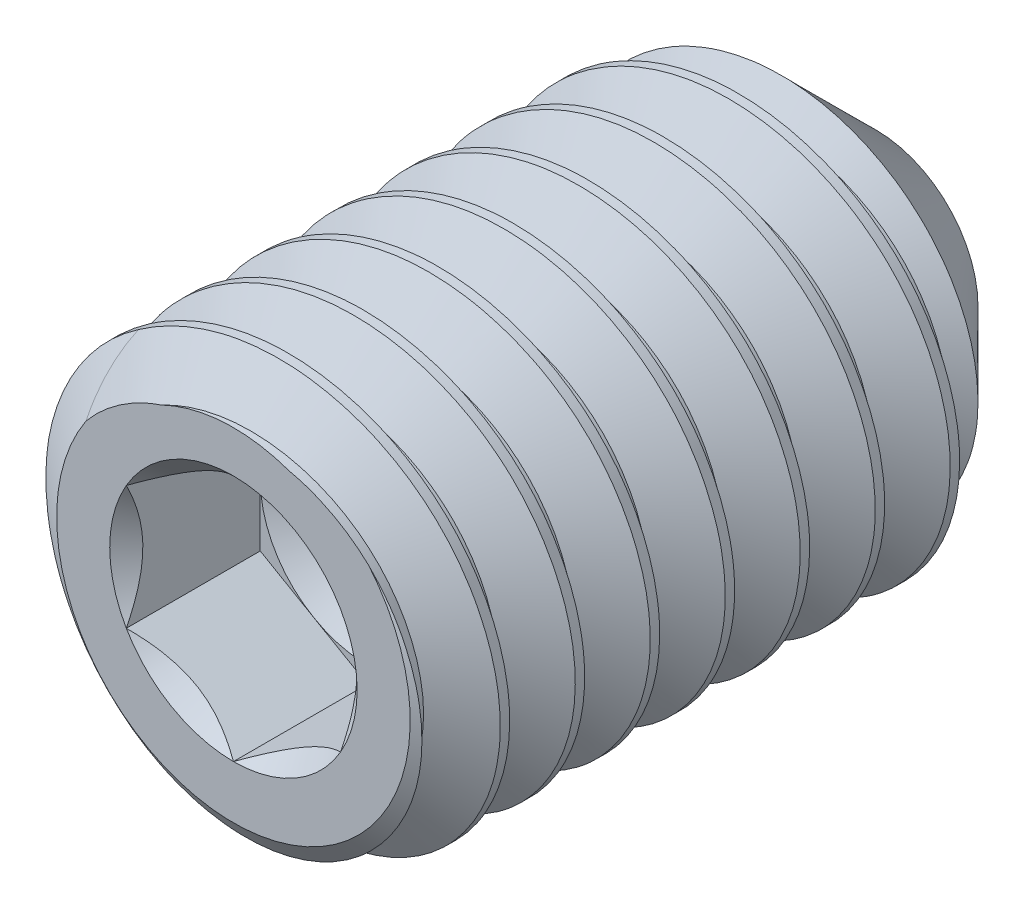
SolidWorks part; units mm, degrees
other "Imported1" parameters "D3"=6.6, "D1"=46.842, "Length"=6, "Drive Size"=2, "Thread Size"=4, "Thread Pitch"=0.7, "hex Depth"=1.25, "D2"=0.9112, "Dia"=12, "D4"=2.3829, "Cup Point Dia"=3.3528, "D5"=1.436, "D6"=1.4986, "D7"=5.0014, "Pitch"=1.75
ref_plane "Front" through (0, 0, 0) normal (0, 0, 1) x (1, 0, 0)
ref_plane "Top" through (0, 0, 0) normal (0, 1, 0) x (1, 0, 0)
ref_plane "Right" through (0, 0, 0) normal (1, 0, 0) x (0, 0, -1)
sketch "Sketch1" plane through (0, 0, 0) normal (1, 0, 0) x (0, 0, -1)
  line L0 (3, 2) -> (-3, 2) construction
  line L1 (-3, 2) -> (-3, -2) construction
  line L2 (-3, -2) -> (3, -2) construction
  line L3 (3, -2) -> (3, 2) construction
  line L4 (-3, 1) -> (-3, -1) construction
  line L5 (2.9562, 2.0758) -> (3.6562, 2.0758) construction
  line L6 (3.6562, 2.0758) -> (3.3062, 1.4696) construction
  line L7 (3.3062, 1.4696) -> (2.9562, 2.0758) construction
  line L8 (2.9781, 2.0379) -> (3.6344, 2.0379) construction
  line L9 (3, 2) -> (3.6125, 2) construction
  line L10 (3.3063, 2.0758) -> (3.3063, 2) construction
  line L11 (3.2625, 1.5453) -> (3.35, 1.5453) construction
  line L12 (3.3062, 1.5453) -> (3.3062, 1.4696) construction
  point P3 (0, 2)
  point P19 (3.3062, 2.0379)
  point P24 (-3, 0)
  point P25 (-3, 0)
  dimension "D1" = 0.0875
sketch "Sketch11" plane through (0, 0, 0) normal (1, 0, 0) x (0, 0, -1)
  line L0 (-3, 0) -> (-3, 1.65)
  line L1 (-3, 1.65) -> (-2.7549, 2)
  line L2 (-2.7549, 2) -> (1.95, 2)
  line L3 (1.95, 2) -> (3, 0.95)
  line L4 (3, 0.95) -> (2.4292, 0)
  line L5 (2.4292, 0) -> (-3, 0)
  line L6 (2.4292, 0) -> (3, 0) construction
  line L7 (3, 0) -> (3, 0.95) construction
  line L8 (3, -0.95) -> (2.4292, 0) construction
  line L9 (-2.7549, -2) -> (1.95, -2) construction
  line L10 (-3, -2) -> (3, -2) construction
  line L11 (-3, 2) -> (-3, -2) construction
  line L12 (3, -2) -> (3, 2) construction
  point P11 (0.55, -2)
  point P12 (-3, 2)
  dimension "D3" = 35
  dimension "D5" = 118
  dimension "D6" = 45
  dimension "D1" = 0.35
  dimension "D2" = 2.45
  dimension "D4" = 1.05
revolve "Revolve1" add sketch "Sketch11" angle 360 about L6
sketch "Sketch2" plane through (0, 0, 3) normal (0, 0, 1) x (1, 0, 0)
  line L1 (0, 1.1547) -> (-1, 0.5774)
  line L2 (-1, 0.5774) -> (-1, -0.5774)
  line L3 (-1, -0.5774) -> (0, -1.1547)
  line L4 (0, -1.1547) -> (1, -0.5774)
  line L5 (1, -0.5774) -> (1, 0.5774)
  line L6 (1, 0.5774) -> (0, 1.1547)
  circle A0 centre (0, 0) radius 1 construction
  circle A1 centre (0, 0) radius 2 construction
extrude "Cut-Extrude1" cut sketch "Sketch2" against normal blind 1.25
sketch "Sketch3" plane through (0, 0, 3) normal (0, 0, 1) x (1, 0, 0)
  circle A0 centre (0, 0) radius 1.1547
extrude "Cut-Extrude2" cut sketch "Sketch3" against normal through all draft 45
sketch "Sketch4" plane through (0, 0, 1.75) normal (0, 0, 1) x (1, 0, 0)
  circle A0 centre (0, 0) radius 1 construction
  circle A1 centre (0, 0) radius 1
extrude "Cut-Extrude3" cut sketch "Sketch4" against normal through all draft 60
sketch "Sketch13" plane through (0, 0, 0) normal (1, 0, 0) x (0, 0, -1)
  line L0 (0, -2) -> (0, 2) construction
  line L2 (-2.7549, 2) -> (1.95, 2) construction
  line L4 (2.4292, 0) -> (-3, 0) construction
  point P0 (-1.5708, 0)
  point P4 (0, 0)
  point P9 (1.5708, 0)
  dimension "D1" = 4
ref_plane "Plane1" through (0, 0, -3) normal (0, 0, 1) x (1, 0, 0)
sketch "Sketch5" plane through (0, 0, -3) normal (0, 0, 1) x (1, 0, 0)
  circle A0 centre (0, 0) radius 2 construction
  circle A1 centre (0, 0) radius 2
curve "Helix/Spiral1" pitch 0.7 height 6.6 radius 2 centre (0, 0, -3) axis (0, 0, 1) start towards (0, 1, 0)
sketch "Sketch6" plane through (0, 0, 0) normal (1, 0, 0) x (0, 0, -1)
  line L0 (2.9562, 2.0758) -> (3.6562, 2.0758) construction
  line L1 (3.6562, 2.0758) -> (3.3062, 1.4696) construction
  line L2 (3.3062, 1.4696) -> (2.9562, 2.0758) construction
  line L3 (3.3062, 2.0758) -> (3.3062, 2) construction
  line L4 (3, 2) -> (3.6125, 2) construction
  line L5 (3.3062, 1.5453) -> (3.3062, 1.4696) construction
  line L6 (3.2625, 1.5453) -> (2.9781, 2.0379)
  line L7 (2.9781, 2.0379) -> (3.6344, 2.0379)
  line L8 (2.9781, 2.0379) -> (3.6344, 2.0379) construction
  line L10 (3.2625, 1.5453) -> (3.35, 1.5453) construction
  line L12 (3.35, 1.5453) -> (3.2625, 1.5453)
  line L13 (3.6344, 2.0379) -> (3.35, 1.5453)
  point P9 (3.3062, 2)
  point P14 (3.3062, 2.0379)
  point P15 (3.3062, 2.0379)
  point P16 (3.3062, 1.5453)
  dimension "D1" = 0.7
  dimension "D2" = 0.0875
sweep "Cut-Sweep1" cut profiles "Sketch6" path "Helix/Spiral1"
equation "\"D3@Helix/Spiral1\" = \"Length@Sketch1\" * 1.1"
equation "\"hex Depth@Cut-Extrude1\" = \"Drive Size@Sketch1\" * .625"
equation "\"D1@Sketch6\" = \"Thread Pitch@Sketch1\""
equation "\"D2@Sketch6\" = \"D1@Sketch6\" / 8"
equation "\"D1@Sketch11\" = \"Thread Pitch@Sketch1\" * .5"
equation "\"D2@Sketch11\" = \"Thread Pitch@Sketch1\" * 3.5"
equation "\"D1@Helix/Spiral1\" = \"Thread Pitch@Sketch1\""
equation "\"D4@Sketch11\" = \"Thread Pitch@Sketch1\" * 1.5"
equation "\"D1@Sketch1\" = \"Thread Pitch@Sketch1\" / 8"
equation "\"D1@Sketch13\"=\"Thread Size@Sketch1\""
